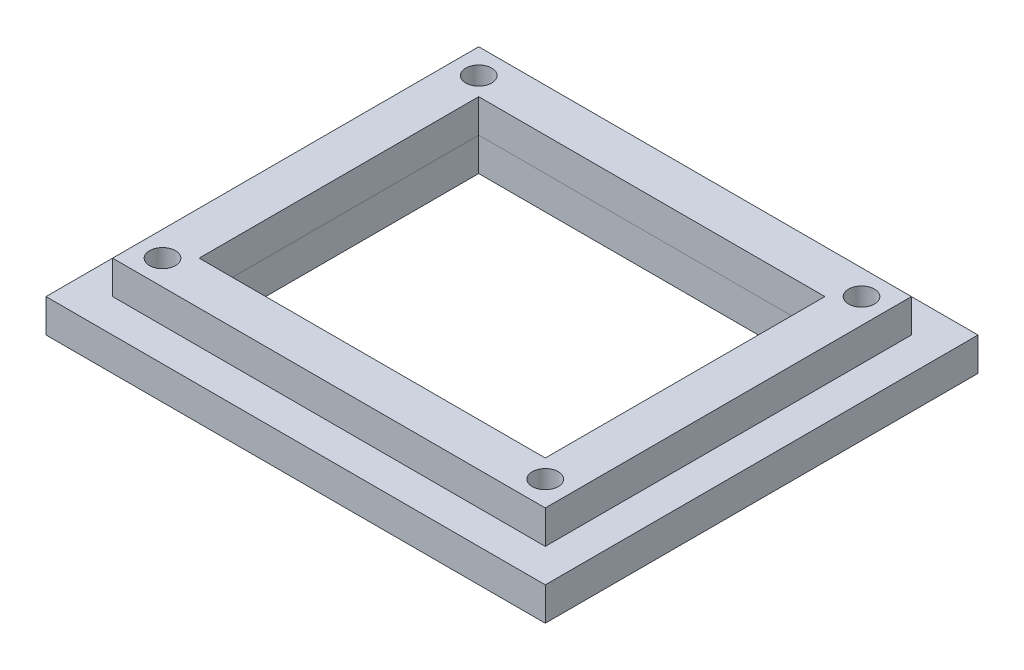
SolidWorks part; units mm, degrees
ref_plane "Front Plane" through (0, 0, 0) normal (0, 0, 1) x (1, 0, 0)
ref_plane "Top Plane" through (0, 0, 0) normal (0, 1, 0) x (1, 0, 0)
ref_plane "Right Plane" through (0, 0, 0) normal (1, 0, 0) x (0, 0, -1)
sketch "Sketch1" plane through (0, 0, 0) normal (0, 1, 0) x (1, 0, 0)
  line L1 (-32.5, 27.5) -> (32.5, 27.5)
  line L2 (-32.5, 27.5) -> (-32.5, -27.5)
  line L3 (-32.5, -27.5) -> (32.5, -27.5)
  line L4 (32.5, 27.5) -> (32.5, -27.5)
  line L5 (-32.5, 27.5) -> (32.5, -27.5) construction
  line L6 (-32.5, -27.5) -> (32.5, 27.5) construction
  line L7 (-28.75, -23.75) -> (28.75, -23.75)
  line L8 (-28.75, -23.75) -> (-28.75, 23.75)
  line L9 (-28.75, 23.75) -> (28.75, 23.75)
  line L10 (28.75, -23.75) -> (28.75, 23.75)
  line L11 (-28.75, -23.75) -> (28.75, 23.75) construction
  line L12 (-28.75, 23.75) -> (28.75, -23.75) construction
  line L13 (-37.5, -32.5) -> (37.5, -32.5)
  line L14 (-37.5, -32.5) -> (-37.5, 32.5)
  line L15 (-37.5, 32.5) -> (37.5, 32.5)
  line L16 (37.5, -32.5) -> (37.5, 32.5)
  line L17 (-37.5, -32.5) -> (37.5, 32.5) construction
  line L18 (-37.5, 32.5) -> (37.5, -32.5) construction
  line L19 (26, -21) -> (-26, -21)
  line L20 (26, -21) -> (26, 21)
  line L21 (26, 21) -> (-26, 21)
  line L22 (-26, -21) -> (-26, 21)
  line L23 (26, -21) -> (-26, 21) construction
  line L24 (26, 21) -> (-26, -21) construction
  circle A0 centre (-28.75, 23.75) radius 1.95
  circle A1 centre (28.75, 23.75) radius 1.95
  circle A2 centre (-28.75, -23.75) radius 1.95
  circle A3 centre (28.75, -23.75) radius 1.95
  point P0 (0, 0)
  point P6 (0, 0)
  point P15 (0, 0)
  point P20 (0, 0)
  dimension "D5" = 3.9
  dimension "D6" = 3.9
  dimension "D7" = 3.9
  dimension "D8" = 3.9
  dimension "D1" = 55
  dimension "D2" = 65
  dimension "D3" = 57.5
  dimension "D4" = 47.5
  dimension "D9" = 65
  dimension "D10" = 75
  dimension "D11" = 42
  dimension "D12" = 52
extrude "Boss-Extrude1" add sketch "Sketch1" along normal blind 5 contours L4 L1 L2 L3 A3 L7 A2 L8 A0 L9 A1 L10 | A3 L10 A1 L9 A0 L8 A2 L7 L19 L22 L21 L20 region at (0, 0, -26.6485) region at (-26.8438, 0, 21.8438)
extrude "Boss-Extrude2" add sketch "Sketch1<3>" against normal blind 5 separate body contours L13 L16 L15 L14 L1 L4 L3 L2 | L4 L1 L2 L3 A3 L7 A2 L8 A0 L9 A1 L10 | A3 L10 A1 L9 A0 L8 A2 L7 L19 L22 L21 L20 | A0 | A2 | A3 | A1 region at (0, 0, -26.6485) region at (-26.8438, 0, 21.8438) region at (-36.5075, 0, 0)
sketch "Sketch1<3>" plane through (0, 0, 0) normal (0, 1, 0) x (1, 0, 0) same geometry as "Sketch1"
sketch "Sketch2" plane through (0, -5, 0) normal (0, -1, 0) x (1, 0, 0)
  line L1 (-30, -25) -> (30, -25)
  line L2 (-30, -25) -> (-30, 25)
  line L3 (-30, 25) -> (30, 25)
  line L4 (30, -25) -> (30, 25)
  line L5 (-30, -25) -> (30, 25) construction
  line L6 (-30, 25) -> (30, -25) construction
  circle A0 centre (-30, 25) radius 1.95
  circle A1 centre (30, 25) radius 1.95
  circle A2 centre (-30, -25) radius 1.95
  circle A3 centre (30, -25) radius 1.95
  point P0 (0, 0)
  dimension "D3" = 3.9
  dimension "D4" = 3.9
  dimension "D5" = 3.9
  dimension "D6" = 3.9
  dimension "D1" = 60
  dimension "D2" = 50
extrude "Cut-Extrude1" cut sketch "Sketch2" against normal blind 5 contours A0 | A2 | A3 | A1
